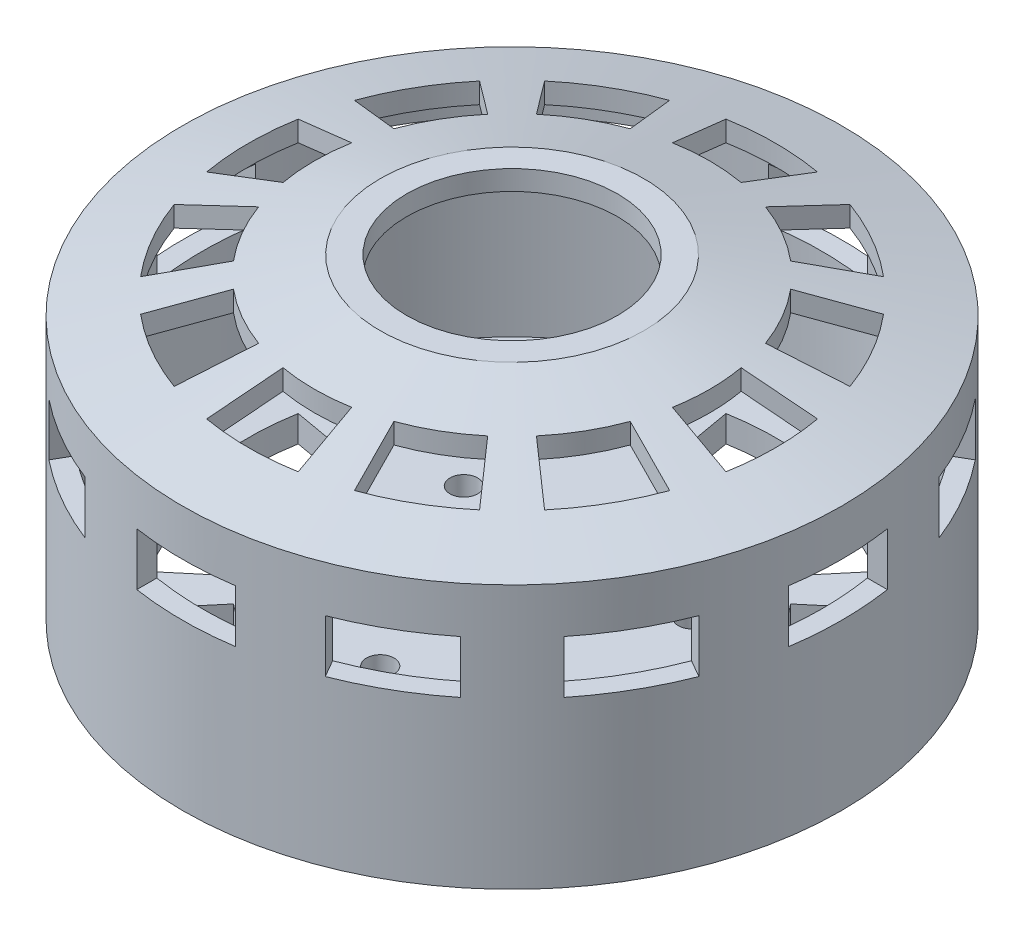
SolidWorks part; units mm, degrees
material "1060 Сплав"
ref_plane "Спереди" through (0, 0, 0) normal (0, 0, 1) x (1, 0, 0)
ref_plane "Сверху" through (0, 0, 0) normal (0, 1, 0) x (1, 0, 0)
ref_plane "Справа" through (0, 0, 0) normal (1, 0, 0) x (0, 0, -1)
other "Configuration Table"
sketch "Эскиз1" plane through (0, 0, 0) normal (0, 1, 0) x (1, 0, 0)
  circle A0 centre (0, 0) radius 50
  dimension "D1" = 100
extrude "Бобышка-Вытянуть1" add sketch "Эскиз1" along normal blind 4
hole_wizard "Сверло под метчик  спиральное M42" positions "Эскиз2" profile "Эскиз3" hole size "M4x0.7" standard "DIN" end condition through all
sketch "Эскиз2" plane through (0, 0, 0) normal (0, -1, 0) x (-1, 0, 0)
  circle A0 centre (0, 0) radius 20 construction
  point P5 (0, 20)
  point P13 (17.3205, 10)
  point P14 (17.3205, -10)
  point P15 (0, -20)
  point P16 (-17.3205, -10)
  point P17 (-17.3205, 10)
  point P19 (17.3205, 10)
  point P20 (0, 0)
  point P21 (0, 0)
  point P22 (0, 0)
  dimension "D1" = 40
  dimension "D2" = 6
sketch "Эскиз3" plane through (-17.3205, 0, -10) normal (1, 0, 0) x (0, 0, -1)
  line L0 (0, 0) -> (0, 4)
  line L1 (0, 4) -> (2.1, 4)
  line L2 (2.1, 4) -> (2.1, 0.4)
  line L3 (2.1, 0.4) -> (2.5, 0)
  line L5 (2.5, 0) -> (0, 0)
  line L6 (-2.1, 0.4) -> (-2.5, 0) construction
  line L11 (0, -6.35) -> (0, 107.95) construction
  dimension "Диаметр сквозного отверстия" = 4.2
  dimension "Глубина сквозного отверстия" = 4
  dimension "Диаметр передней зенковки" = 5
  dimension "Угол передней зенковки" = 90
sketch "Эскиз7" plane through (0, 0, 0) normal (0, 0, 1) x (1, 0, 0)
  line L2 (50, 4) -> (50, 40)
  line L3 (50, 40) -> (20, 48.0385)
  line L4 (20, 48.0385) -> (16, 48.0385)
  line L5 (16, 48.0385) -> (16, 45.0385)
  line L6 (16, 45.0385) -> (19.605, 45.0385)
  line L7 (19.605, 45.0385) -> (47, 37.698)
  line L8 (47, 37.698) -> (47, 4)
  line L9 (0, -1000) -> (0, 49000) construction
  line L10 (50, 4) -> (-50, 4) construction
  line L11 (50, 4) -> (-50, 4) construction
  line L12 (-50, 0) -> (50, 0) construction
  line L13 (47, 4) -> (50, 4)
  dimension "D1" = 3
  dimension "D2" = 3
  dimension "D3" = 3
  dimension "D4" = 40
  dimension "D5" = 40
  dimension "D6" = 15
  dimension "D7" = 32
revolve "Повернуть1" add sketch "Эскиз7" angle 360 about L9 region at (48.5, 4.5564, 0)
sketch "Эскиз4" plane through (0, 0, 0) normal (0, -1, 0) x (1, 0, 0)
  line L0 (0, 0) -> (0, 40) construction
  line L1 (-6.9459, 39.3923) -> (-5.2094, 29.5442)
  line L2 (6.9459, 39.3923) -> (5.2094, 29.5442)
  line L3 (13.6808, 37.5877) -> (10.2606, 28.1908)
  line L4 (25.7115, 30.6418) -> (19.2836, 22.9813)
  line L5 (0, 0) -> (20, 34.641) construction
  line L6 (30.6418, 25.7115) -> (22.9813, 19.2836)
  line L7 (37.5877, 13.6808) -> (28.1908, 10.2606)
  line L8 (0, 0) -> (34.641, 20) construction
  line L9 (39.3923, 6.9459) -> (29.5442, 5.2094)
  line L10 (39.3923, -6.9459) -> (29.5442, -5.2094)
  line L11 (0, 0) -> (40, 0) construction
  line L12 (37.5877, -13.6808) -> (28.1908, -10.2606)
  line L13 (30.6418, -25.7115) -> (22.9813, -19.2836)
  line L14 (0, 0) -> (34.641, -20) construction
  line L15 (25.7115, -30.6418) -> (19.2836, -22.9813)
  line L16 (13.6808, -37.5877) -> (10.2606, -28.1908)
  line L17 (0, 0) -> (20, -34.641) construction
  line L18 (6.9459, -39.3923) -> (5.2094, -29.5442)
  line L19 (-6.9459, -39.3923) -> (-5.2094, -29.5442)
  line L20 (0, 0) -> (0, -40) construction
  line L21 (-13.6808, -37.5877) -> (-10.2606, -28.1908)
  line L22 (-25.7115, -30.6418) -> (-19.2836, -22.9813)
  line L23 (0, 0) -> (-20, -34.641) construction
  line L24 (-30.6418, -25.7115) -> (-22.9813, -19.2836)
  line L25 (-37.5877, -13.6808) -> (-28.1908, -10.2606)
  line L26 (0, 0) -> (-34.641, -20) construction
  line L27 (-39.3923, -6.9459) -> (-29.5442, -5.2094)
  line L28 (-39.3923, 6.9459) -> (-29.5442, 5.2094)
  line L29 (0, 0) -> (-40, 0) construction
  line L30 (-37.5877, 13.6808) -> (-28.1908, 10.2606)
  line L31 (-30.6418, 25.7115) -> (-22.9813, 19.2836)
  line L32 (0, 0) -> (-34.641, 20) construction
  line L33 (-25.7115, 30.6418) -> (-19.2836, 22.9813)
  line L34 (-13.6808, 37.5877) -> (-10.2606, 28.1908)
  line L35 (0, 0) -> (-20, 34.641) construction
  arc A0 (6.9459, 39.3923) -> (-6.9459, 39.3923) centre (0, 0) ccw
  arc A1 (5.2094, 29.5442) -> (-5.2094, 29.5442) centre (0, 0) ccw
  arc A2 (25.7115, 30.6418) -> (13.6808, 37.5877) centre (0, 0) ccw
  arc A3 (19.2836, 22.9813) -> (10.2606, 28.1908) centre (0, 0) ccw
  arc A4 (37.5877, 13.6808) -> (30.6418, 25.7115) centre (0, 0) ccw
  arc A5 (28.1908, 10.2606) -> (22.9813, 19.2836) centre (0, 0) ccw
  arc A6 (39.3923, -6.9459) -> (39.3923, 6.9459) centre (0, 0) ccw
  arc A7 (29.5442, -5.2094) -> (29.5442, 5.2094) centre (0, 0) ccw
  arc A8 (30.6418, -25.7115) -> (37.5877, -13.6808) centre (0, 0) ccw
  arc A9 (22.9813, -19.2836) -> (28.1908, -10.2606) centre (0, 0) ccw
  arc A10 (13.6808, -37.5877) -> (25.7115, -30.6418) centre (0, 0) ccw
  arc A11 (10.2606, -28.1908) -> (19.2836, -22.9813) centre (0, 0) ccw
  arc A12 (-6.9459, -39.3923) -> (6.9459, -39.3923) centre (0, 0) ccw
  arc A13 (-5.2094, -29.5442) -> (5.2094, -29.5442) centre (0, 0) ccw
  arc A14 (-25.7115, -30.6418) -> (-13.6808, -37.5877) centre (0, 0) ccw
  arc A15 (-19.2836, -22.9813) -> (-10.2606, -28.1908) centre (0, 0) ccw
  arc A16 (-37.5877, -13.6808) -> (-30.6418, -25.7115) centre (0, 0) ccw
  arc A17 (-28.1908, -10.2606) -> (-22.9813, -19.2836) centre (0, 0) ccw
  arc A18 (-39.3923, 6.9459) -> (-39.3923, -6.9459) centre (0, 0) ccw
  arc A19 (-29.5442, 5.2094) -> (-29.5442, -5.2094) centre (0, 0) ccw
  arc A20 (-30.6418, 25.7115) -> (-37.5877, 13.6808) centre (0, 0) ccw
  arc A21 (-22.9813, 19.2836) -> (-28.1908, 10.2606) centre (0, 0) ccw
  arc A22 (-13.6808, 37.5877) -> (-25.7115, 30.6418) centre (0, 0) ccw
  arc A23 (-10.2606, 28.1908) -> (-19.2836, 22.9813) centre (0, 0) ccw
  point P65 (0, 0)
  dimension "D1" = 40
  dimension "D2" = 30
  dimension "D3" = 20
  dimension "D4" = 12
extrude "Вырез-Вытянуть1" cut sketch "Эскиз4" against normal through all
sketch "Эскиз11" plane through (0, 0, 0) normal (1, 0, 0) x (0, 0, -1)
  line L0 (0, -1000) -> (0, 49000) construction
  line L2 (-7.5, 25) -> (7.5, 25)
  line L3 (-7.5, 25) -> (-7.5, 33)
  line L4 (-7.5, 33) -> (7.5, 33)
  line L5 (7.5, 25) -> (7.5, 33)
  line L6 (-7.5, 25) -> (7.5, 33) construction
  line L7 (-7.5, 33) -> (7.5, 25) construction
  point P1 (0, 29)
  dimension "D1" = 15
  dimension "D2" = 8
  dimension "D3" = 25
extrude "Вырез-Вытянуть2" cut sketch "Эскиз11" against normal through all
pattern_circular "Круговой массив1" count 12 over 360 about axis through (0, -1000, 0) along (0, 1, 0) of "Вырез-Вытянуть2"
